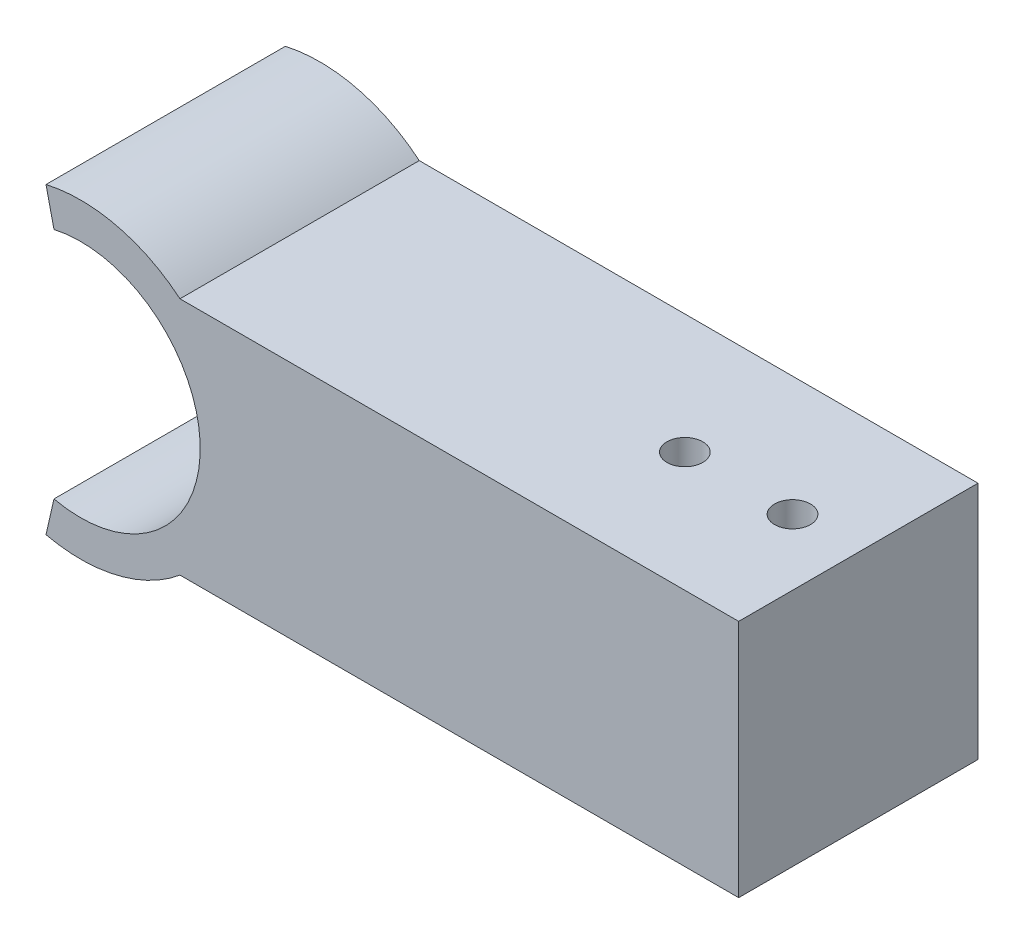
SolidWorks part; units mm, degrees
ref_plane "Спереди" through (0, 0, 0) normal (0, 0, 1) x (1, 0, 0)
ref_plane "Сверху" through (0, 0, 0) normal (0, 1, 0) x (1, 0, 0)
ref_plane "Справа" through (0, 0, 0) normal (1, 0, 0) x (0, 0, -1)
sketch "Эскиз1" plane through (0, 0, 0) normal (0, 0, 1) x (1, 0, 0)
  line L0 (-2.222, 9.75) -> (-2.8887, 12.675)
  line L1 (-2.222, -9.75) -> (-2.8887, -12.675)
  line L2 (0, 0) -> (10, 0) construction
  line L3 (0, 0) -> (-2.222, -9.75) construction
  line L4 (55, -10) -> (8.3066, -10)
  line L5 (10, 0) -> (55, 0) construction
  line L6 (55, 0) -> (55, -10)
  line L11 (8.3066, 10) -> (55, 10)
  line L12 (55, 10) -> (55, 0)
  arc A0 (-2.222, 9.75) -> (-2.222, -9.75) centre (0, 0) cw
  arc A2 (-2.8887, 12.675) -> (8.3066, 10) centre (0, 0) cw
  arc A3 (-2.8887, -12.675) -> (8.3066, -10) centre (0, 0) ccw
  dimension "D1" = 10
  dimension "D4" = 46.6934
  dimension "D2" = 3
  dimension "D3" = 19.5
  dimension "D5" = 10
extrude "Бобышка-Вытянуть1" add sketch "Эскиз1" along normal blind 20
sketch "Эскиз2" plane through (0, 10, 0) normal (0, 1, 0) x (1, 0, 0)
  line L2 (40.5, -10) -> (45, -10) construction
  line L4 (45, -10) -> (45, 0) construction
  line L6 (45, -10) -> (49.5, -10) construction
  line L7 (55, 0) -> (8.3066, 0) construction
  line L8 (45, -10) -> (45, -20) construction
  line L9 (55, -20) -> (8.3066, -20) construction
  line L10 (55, -20) -> (55, 0) construction
  circle A0 centre (40.5, -10) radius 1.5
  circle A1 centre (49.5, -10) radius 1.5
  point P0 (49.7346, -10)
  dimension "D1" = 3
  dimension "D2" = 4.5
  dimension "D3" = 10
sketch "Эскиз4" plane through (0, 10, 0) normal (0, 1, 0) x (1, 0, 0)
extrude "Вырез-Вытянуть1" cut sketch "Эскиз2" against normal through all
